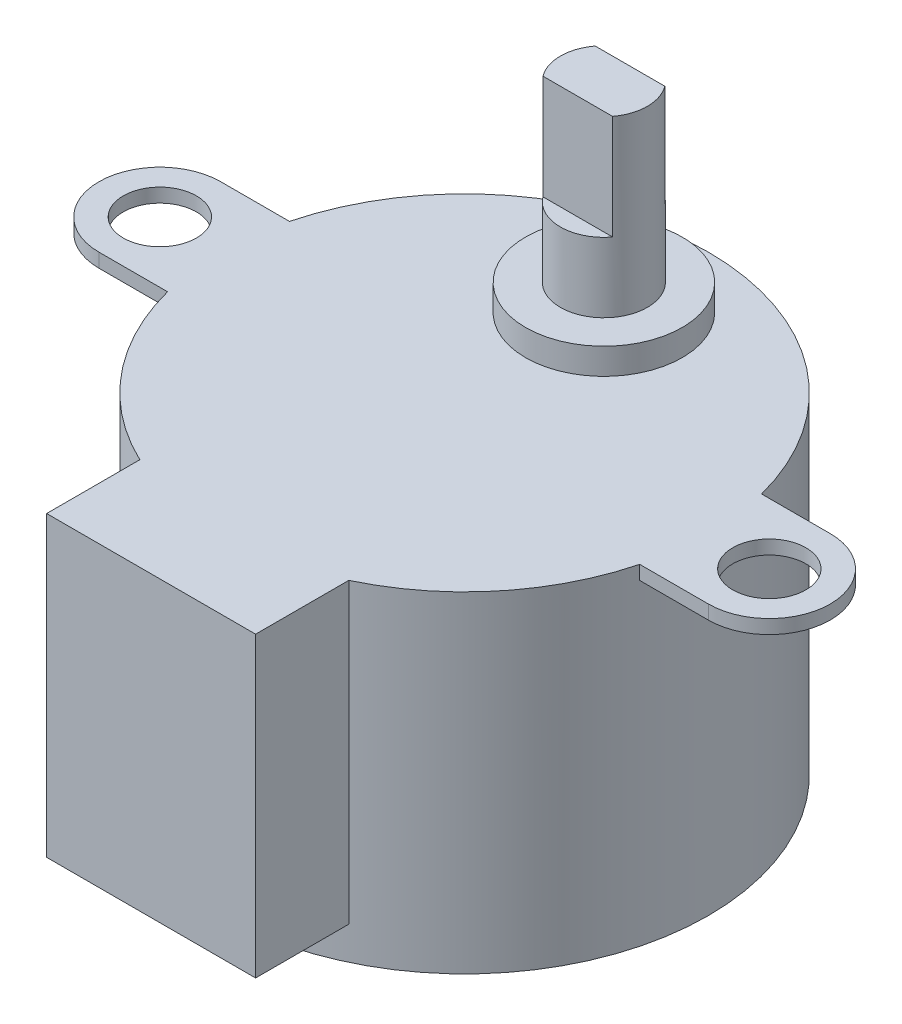
SolidWorks part; units mm, degrees
ref_plane "Alzado" through (0, 0, 0) normal (0, 0, 1) x (1, 0, 0)
ref_plane "Planta" through (0, 0, 0) normal (0, 1, 0) x (1, 0, 0)
ref_plane "Vista lateral" through (0, 0, 0) normal (1, 0, 0) x (0, 0, -1)
sketch "Croquis1" plane through (0, 0, 0) normal (0, 1, 0) x (1, 0, 0)
  circle A0 centre (0, 0) radius 14
  dimension "D1" = 28
extrude "Saliente-Extruir1" add sketch "Croquis1" along normal blind 19
sketch "Croquis2" plane through (0, 19, 0) normal (0, 1, 0) x (1, 0, 0)
  line L0 (-17.5, 3.5) -> (-13.5554, 3.5)
  line L1 (-17.5, -3.5) -> (-13.5554, -3.5)
  line L2 (17.5, -3.5) -> (13.5554, -3.5)
  line L3 (17.5, 3.5) -> (13.5554, 3.5)
  circle A0 centre (-17.5, 0) radius 2.1
  circle A1 centre (17.5, 0) radius 2.1
  arc A2 (-17.5, 3.5) -> (-17.5, -3.5) centre (-17.5, 0) ccw
  arc A3 (17.5, -3.5) -> (17.5, 3.5) centre (17.5, 0) ccw
  circle A4 centre (0, 0) radius 14 construction
  arc A5 (-13.5554, -3.5) -> (13.5554, -3.5) centre (0, 0) ccw
  arc A6 (13.5554, 3.5) -> (-13.5554, 3.5) centre (0, 0) ccw
  dimension "D1" = 7
  dimension "D2" = 4.2
  dimension "D3" = 4.2
  dimension "D4" = 7
  dimension "D5" = 35
  dimension "D6" = 17.5
extrude "Saliente-Extruir2" add sketch "Croquis2" against normal blind 0.8
sketch "Croquis3" plane through (0, 0, 0) normal (0, 0, 1) x (1, 0, 0)
  line L0 (13.5554, 19) -> (-13.5554, 19) construction
  line L1 (-6, 19) -> (6, 19)
  line L2 (-6, 19) -> (-6, 1.9)
  line L3 (-6, 1.9) -> (6, 1.9)
  line L4 (6, 19) -> (6, 1.9)
  line L5 (-14, 0) -> (14, 0) construction
  point P6 (0, 19)
  dimension "D1" = 12
  dimension "D2" = 1.9
extrude "Saliente-Extruir3" add sketch "Croquis3" against normal up to surface (5.3509 mm away) from offset 18 up to face at (0, 18.6, 0)
sketch "Croquis4" plane through (0, 19, 0) normal (0, 1, 0) x (1, 0, 0)
  circle A0 centre (0, 8) radius 4.5
  point P2 (0, 0)
  point P4 (0, 0)
  dimension "D1" = 9
  dimension "D2" = 8
extrude "Saliente-Extruir4" add sketch "Croquis4" along normal blind 1.5
sketch "Croquis5" plane through (0, 20.5, 0) normal (0, 1, 0) x (1, 0, 0)
  circle A0 centre (0, 8) radius 2.5
  circle A1 centre (0, 8) radius 4.5 construction
  point P2 (0, 0)
  dimension "D1" = 5
extrude "Saliente-Extruir5" add sketch "Croquis5" along normal blind 10
sketch "Croquis7" plane through (0, 30.5, 0) normal (0, 1, 0) x (1, 0, 0)
  line L0 (-2.5, 8) -> (2.5, 8) construction
  line L2 (3.3151, 9.5) -> (-3.2429, 9.5)
  line L3 (3.3151, 9.5) -> (3.3151, 10.8684)
  line L4 (3.3151, 10.8684) -> (-3.2429, 10.8684)
  line L5 (-3.2429, 9.5) -> (-3.2429, 10.8684)
  line L6 (3.1602, 4.5119) -> (-3.2429, 4.5119)
  line L7 (3.1602, 4.5119) -> (3.1602, 6.5)
  line L8 (3.1602, 6.5) -> (-3.2429, 6.5)
  line L9 (-3.2429, 4.5119) -> (-3.2429, 6.5)
  circle A0 centre (0, 8) radius 2.5 construction
  circle A1 centre (0, 8) radius 2.5 construction
  dimension "D1" = 1.5
  dimension "D2" = 1.5
extrude "Cortar-Extruir1" cut sketch "Croquis7" against normal blind 6
